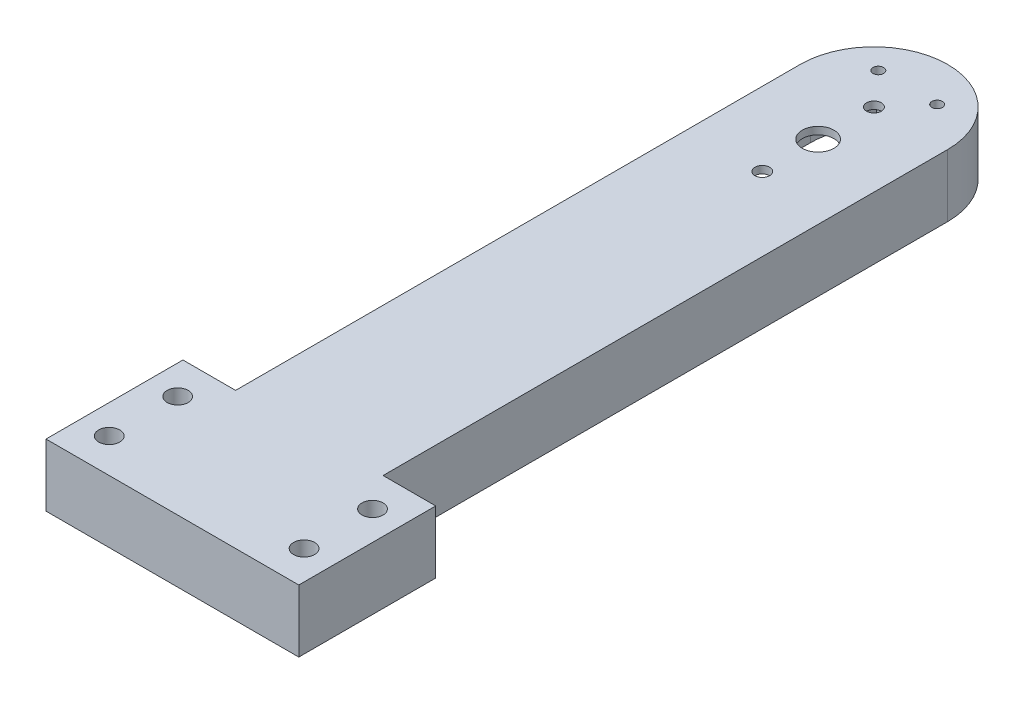
SolidWorks part; units mm, degrees
ref_plane "Front Plane" through (0, 0, 0) normal (0, 0, 1) x (1, 0, 0)
ref_plane "Top Plane" through (0, 0, 0) normal (0, 1, 0) x (1, 0, 0)
ref_plane "Right Plane" through (0, 0, 0) normal (1, 0, 0) x (0, 0, -1)
sketch "Sketch1" plane through (0, 0, 0) normal (0, 1, 0) x (1, 0, 0)
  line L0 (-5.6852, 33.5) -> (5.6852, 33.5)
  line L1 (0, 0) -> (0, 26.5) construction
  line L2 (0, 26.5) -> (0, 33.5) construction
  line L3 (-5.6852, 33.5) -> (-11.4774, 17.5861)
  line L4 (0, 0) -> (-21, 0) construction
  line L5 (5.6852, 33.5) -> (11.4774, 17.5861)
  line L6 (5.6852, -33.5) -> (11.4774, -17.5861)
  line L7 (-5.6852, -33.5) -> (5.6852, -33.5)
  line L8 (-5.6852, -33.5) -> (-11.4774, -17.5861)
  line L9 (0, 0) -> (0, -243.5) construction
  line L11 (-30, 26.5) -> (-30, -243.5)
  line L12 (-30, -243.5) -> (30, -243.5)
  line L13 (30, 26.5) -> (30, -243.5)
  arc A0 (-11.4774, 17.5861) -> (-11.4774, -17.5861) centre (0, 0) ccw
  circle A1 centre (0, 26.5) radius 3.5
  circle A2 centre (0, -26.5) radius 3.5
  arc A3 (11.4774, -17.5861) -> (11.4774, 17.5861) centre (0, 0) ccw
  arc A5 (30, 26.5) -> (-30, 26.5) centre (0, 26.5) ccw
  point P1 (0, 56.5)
  dimension "D1" = 11.3704
  dimension "D2" = 42
  dimension "D4" = 7
  dimension "D6" = 7
  dimension "D3" = 33.5
  dimension "D5" = 110
  dimension "D7" = 300
  dimension "D8" = 30
extrude "Boss-Extrude1" add sketch "Sketch1" along normal blind 10 contours L13 A5 L11 L12 A3 L6 L7 L8 A0 L3 L0 L5 region at (0, 0, 107.816)
sketch "Sketch2" plane through (0, 10, 0) normal (0, 1, 0) x (1, 0, 0)
  line L0 (5.6852, 33.5) -> (11.4774, 17.5861) construction
  line L1 (5.6852, -33.5) -> (11.4774, -17.5861) construction
  line L2 (-5.6852, -33.5) -> (5.6852, -33.5) construction
  line L3 (-5.6852, -33.5) -> (-11.4774, -17.5861) construction
  line L4 (-5.6852, 33.5) -> (-11.4774, 17.5861) construction
  line L5 (-5.6852, 33.5) -> (5.6852, 33.5) construction
  line L6 (5.6852, 33.5) -> (11.4774, 17.5861)
  line L7 (5.6852, -33.5) -> (11.4774, -17.5861)
  line L8 (-5.6852, -33.5) -> (5.6852, -33.5)
  line L9 (-5.6852, -33.5) -> (-11.4774, -17.5861)
  line L10 (-5.6852, 33.5) -> (-11.4774, 17.5861)
  line L11 (-5.6852, 33.5) -> (5.6852, 33.5)
  line L12 (-21, 0) -> (0, 0) construction
  arc A0 (11.4774, -17.5861) -> (11.4774, 17.5861) centre (0, 0) ccw construction
  arc A1 (-11.4774, 17.5861) -> (-11.4774, -17.5861) centre (0, 0) ccw construction
  arc A2 (11.4774, -17.5861) -> (11.4774, 17.5861) centre (0, 0) ccw
  arc A3 (-11.4774, 17.5861) -> (-11.4774, -17.5861) centre (0, 0) ccw
  circle A4 centre (0, 26.5) radius 3.5
  circle A5 centre (0, -26.5) radius 3.5
  circle A6 centre (0, 0) radius 7.5
  dimension "D2" = 7
  dimension "D1" = 7
extrude "Boss-Extrude2" add sketch "Sketch2" against normal blind 3.5
sketch "Sketch3" plane through (0, 0, 0) normal (0, -1, 0) x (1, 0, 0)
  line L4 (30, -26.5) -> (30, 243.5) construction
  line L5 (-30, -26.5) -> (-30, 243.5) construction
  line L6 (35, 243.5) -> (35, -26.5)
  line L7 (-35, -26.5) -> (-35, 243.5)
  line L8 (35, 243.5) -> (35, -26.5)
  line L9 (-35, -26.5) -> (-35, 243.5)
  line L10 (30, -26.5) -> (30, 243.5)
  line L11 (-30, -26.5) -> (-30, 243.5)
  line L12 (-35, 243.5) -> (-30, 243.5)
  line L13 (30, 243.5) -> (35, 243.5)
  line L14 (-27.9106, -37.5) -> (27.9106, -37.5)
  line L15 (5.6852, -33.5) -> (-5.6852, -33.5) construction
  line L16 (0, -56.5) -> (0, -37.5) construction
  arc A2 (-30, -26.5) -> (30, -26.5) centre (0, -26.5) ccw construction
  arc A3 (-35, -26.5) -> (35, -26.5) centre (0, -26.5) ccw
  arc A4 (-35, -26.5) -> (35, -26.5) centre (0, -26.5) ccw
  arc A5 (-30, -26.5) -> (-27.9106, -37.5) centre (0, -26.5) ccw
  arc A6 (27.9106, -37.5) -> (30, -26.5) centre (0, -26.5) ccw
  dimension "D2" = 4
  dimension "D3" = 19
  dimension "D1" = 5
extrude "Boss-Extrude3" add sketch "Sketch3" against normal up to surface (10 mm away) and the other way blind 19.65 up to face at (0, 10, 101)
sketch "Sketch4" plane through (0, -19.65, 0) normal (0, -1, 0) x (1, 0, 0)
  line L0 (-27.9106, -37.5) -> (-27.9106, -47.6187) construction
  line L1 (-27.9106, -47.6187) -> (27.9106, -47.6187) construction
  line L2 (27.9106, -47.6187) -> (27.9106, -37.5) construction
  line L3 (-27.9106, -42.5594) -> (0, -42.5594) construction
  line L4 (0, -42.5594) -> (0, -37.5) construction
  line L5 (27.9106, -37.5) -> (-27.9106, -37.5) construction
  arc A0 (-35, -26.5) -> (35, -26.5) centre (0, -26.5) ccw construction
  circle A1 centre (-13.9553, -42.5594) radius 2.5
  circle A2 centre (13.9553, -42.5594) radius 2.5
extrude "Cut-Extrude1" cut sketch "Sketch4" against normal through all
sketch "Sketch5" plane through (0, 10, 0) normal (0, 1, 0) x (1, 0, 0)
  line L0 (0, -243.5) -> (0, -274) construction
  line L7 (-35, -243.5) -> (35, -243.5) construction
  line L9 (32.5, -290.25) -> (60, -290.25) construction
  line L10 (-60, -306.5) -> (60, -306.5)
  line L11 (-60, -306.5) -> (-60, -241.5)
  line L12 (-60, -241.5) -> (60, -241.5)
  line L13 (60, -306.5) -> (60, -241.5)
  line L14 (-60, -306.5) -> (60, -241.5) construction
  line L15 (-60, -241.5) -> (60, -306.5) construction
  line L16 (32.5, -274) -> (60, -274) construction
  line L17 (32.5, -274) -> (32.5, -306.5) construction
  circle A1 centre (46.25, -290.25) radius 5
  circle A2 centre (-46.25, -290.25) radius 5
  circle A3 centre (46.25, -257.75) radius 5
  circle A4 centre (-46.25, -257.75) radius 5
  dimension "D2" = 120
  dimension "D3" = 65
  dimension "D1" = 2
extrude "Boss-Extrude4" add sketch "Sketch5" against normal up to surface (29.65 mm away) up to face at (-13.9553, -19.65, -45.0594)
sketch "Sketch6" plane through (0, -19.65, 0) normal (0, -1, 0) x (1, 0, 0)
  line L0 (-60, 274) -> (60, 274) construction
  line L1 (-60, 241.5) -> (-60, 306.5) construction
  line L2 (60, 306.5) -> (60, 241.5) construction
  line L3 (30, 241.5) -> (-30, 241.5) construction
  line L5 (-30, 296.5) -> (-30, 241.5)
  line L6 (-30, 241.5) -> (30, 241.5)
  line L7 (30, 296.5) -> (30, 241.5)
  line L8 (-30, 306.5) -> (30, 241.5) construction
  line L9 (-30, 241.5) -> (30, 306.5) construction
  line L10 (-30, 296.5) -> (30, 296.5)
  point P6 (0, 274)
extrude "Cut-Extrude2" cut sketch "Sketch6" against normal up to surface (19.65 mm away) up to face at (0, 0, 0)
sketch "Sketch7" plane through (0, 10, 0) normal (0, 1, 0) x (1, 0, 0)
  line L0 (-46.25, -257.75) -> (-60, -257.75) construction
  line L1 (-60, -241.5) -> (-60, -306.5) construction
